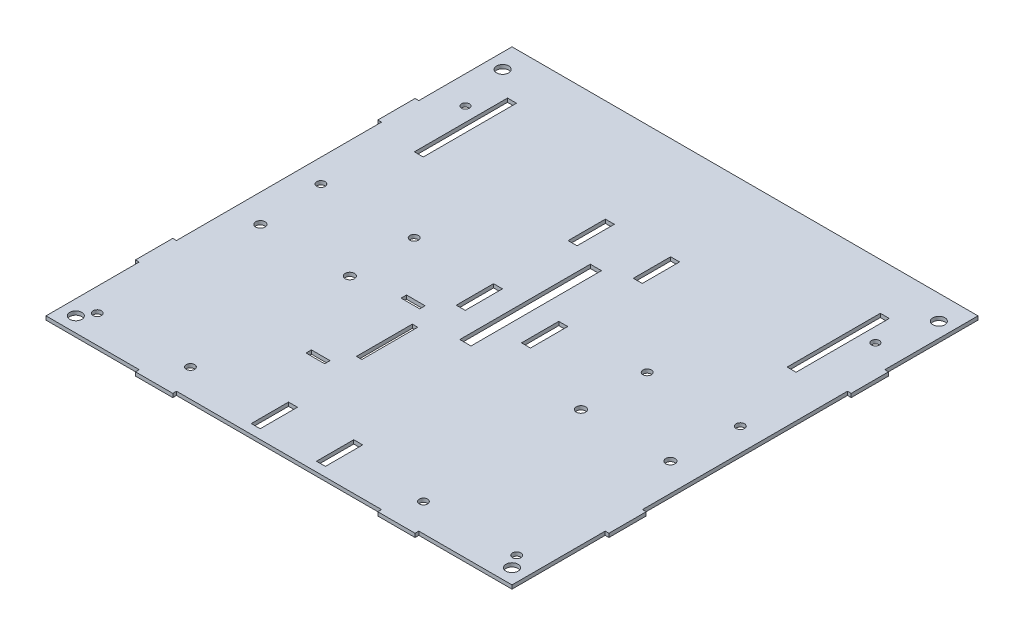
SolidWorks part; units mm, degrees
ref_plane "Front Plane" through (0, 0, 0) normal (0, 0, 1) x (1, 0, 0)
ref_plane "Top Plane" through (0, 0, 0) normal (0, 1, 0) x (1, 0, 0)
ref_plane "Right Plane" through (0, 0, 0) normal (1, 0, 0) x (0, 0, -1)
sketch "Sketch1" plane through (0, 0, 0) normal (0, 1, 0) x (1, 0, 0)
  line L0 (144.9, 25) -> (144.9, 5)
  line L1 (144.9, 5) -> (140.1, 5)
  line L2 (140.1, 25) -> (144.9, 25)
  line L3 (140.1, 5) -> (140.1, 25)
  line L4 (109.9, 5) -> (109.9, 25)
  line L5 (109.9, 25) -> (105.1, 25)
  line L6 (105.1, 25) -> (105.1, 5)
  line L7 (105.1, 5) -> (109.9, 5)
  line L8 (87, 52.4842) -> (97, 52.4842)
  line L9 (97, 55.3842) -> (97, 52.4842)
  line L10 (87, 55.3842) -> (97, 55.3842)
  line L11 (87, 52.4842) -> (87, 55.3842)
  line L12 (105, 64.4342) -> (102.1, 64.4342)
  line L13 (105, 64.4342) -> (105, 94.4342)
  line L14 (102.1, 94.4342) -> (102.1, 64.4342)
  line L15 (102.1, 94.4342) -> (105, 94.4342)
  line L16 (97, 106.3842) -> (97, 103.4842)
  line L17 (97, 106.3842) -> (87, 106.3842)
  line L18 (87, 103.4842) -> (97, 103.4842)
  line L19 (87, 103.4842) -> (87, 106.3842)
  line L20 (109.9, 135) -> (105.1, 135)
  line L21 (109.9, 115) -> (109.9, 135)
  line L22 (105.1, 135) -> (105.1, 115)
  line L23 (105.1, 115) -> (109.9, 115)
  line L24 (144.9, 115) -> (140.1, 115)
  line L25 (140.1, 115) -> (140.1, 135)
  line L26 (144.9, 135) -> (144.9, 115)
  line L27 (140.1, 135) -> (144.9, 135)
  line L28 (227.4, 175) -> (227.4, 225)
  line L29 (222.6, 175) -> (222.6, 225)
  line L30 (227.4, 225) -> (222.6, 225)
  line L31 (222.6, 175) -> (227.4, 175)
  line L32 (125, 100) -> (125, 170) construction
  line L33 (122, 170) -> (128, 170)
  line L34 (122, 170) -> (122, 100)
  line L35 (122, 100) -> (128, 100)
  line L36 (22.6, 225) -> (27.4, 225)
  line L37 (27.4, 225) -> (27.4, 175)
  line L38 (22.6, 175) -> (22.6, 225)
  line L39 (27.4, 175) -> (22.6, 175)
  line L40 (250, 250) -> (0, 250)
  line L41 (0, 250) -> (0, 0)
  line L42 (0, 0) -> (250, 0)
  line L43 (250, 0) -> (250, 250)
  line L44 (128, 170) -> (128, 100)
  dimension "D2" = 22.6
  dimension "D3" = 5.1
  dimension "D4" = 10
  dimension "D5" = 102.1
  dimension "D6" = 2.9
  dimension "D7" = 27.4
  dimension "D8" = 105.1
  dimension "D9" = 4.8
  dimension "D10" = 140.1
  dimension "D11" = 222.6
  dimension "D12" = 5
  dimension "D13" = 25
  dimension "D14" = 52.4842
  dimension "D15" = 250
  dimension "D16" = 64.4342
  dimension "D17" = 103.4842
  dimension "D18" = 94.4342
  dimension "D19" = 115
  dimension "D20" = 50
  dimension "D21" = 6
  dimension "D22" = 70
  dimension "D23" = 175
  dimension "D24" = 125
  dimension "D25" = 250
  dimension "D26" = 80
extrude "Boss-Extrude1" add sketch "Sketch1" along normal blind 2
sketch "Sketch2" plane through (0, 2, 0) normal (0, 1, 0) x (1, 0, 0)
  line L0 (0, 250) -> (0, 0) construction
  line L1 (0, 0) -> (250, 0) construction
  circle A0 centre (15, 100) radius 2.5
  circle A1 centre (63, 100) radius 2.5
  dimension "D1" = 5
  dimension "D2" = 5
  dimension "D3" = 48
  dimension "D4" = 15
  dimension "D5" = 100
extrude "Cut-Extrude1" cut sketch "Sketch2" against normal through all
sketch "Sketch3" plane through (0, 2, 0) normal (0, 1, 0) x (1, 0, 0)
  line L3 (250, 0) -> (250, 250) construction
  circle A0 centre (8, 8) radius 3.25
  circle A1 centre (8, 237) radius 3.25
  dimension "D1" = 6.5
  dimension "D2" = 242
  dimension "D3" = 212
  dimension "D4" = 17
extrude "Cut-Extrude2" cut sketch "Sketch3" against normal through all
ref_plane "Plane1" through (125, 0, 0) normal (-1, 0, 0) x (0, 0, 1)
mirror "Mirror1" about plane through (125, 0, 0) normal (-1, 0, 0) of "Cut-Extrude2"
sketch "Sketch4" plane through (0, 2, 0) normal (0, 1, 0) x (1, 0, 0)
  line L1 (0, 200) -> (-2, 200)
  line L2 (0, 200) -> (0, 180)
  line L3 (0, 180) -> (-2, 180)
  line L4 (-2, 200) -> (-2, 180)
  line L7 (0, 70) -> (-2, 70)
  line L8 (0, 70) -> (0, 50)
  line L9 (0, 50) -> (-2, 50)
  line L10 (-2, 70) -> (-2, 50)
  line L11 (144.9, 5) -> (144.9, 25) construction
  line L12 (50, 0) -> (70, 0)
  line L13 (50, 0) -> (50, -2)
  line L14 (50, -2) -> (70, -2)
  line L15 (70, 0) -> (70, -2)
  line L16 (144.9, 25) -> (140.1, 25) construction
  dimension "D1" = 74.9
  dimension "D2" = 94.9
  dimension "D3" = 144.9
  dimension "D4" = 146.9
  dimension "D5" = 25
  dimension "D6" = 155
  dimension "D7" = 25
extrude "Boss-Extrude2" add sketch "Sketch4" against normal up to vertex (2 mm away) up to point (0, 0, 0)
mirror "Mirror2" about plane through (125, 0, 0) normal (-1, 0, 0) of "Boss-Extrude2"
mirror "Mirror3" about plane through (125, 0, 0) normal (-1, 0, 0) of "Cut-Extrude1"
hole_wizard "Ø4.5 (4.5) Diameter Hole1" positions "Sketch7" profile "Sketch6" hole size "Ø4.5" standard "ISO"
sketch "Sketch7" plane through (0, 2, 0) normal (0, 1, 0) x (1, 0, 0)
  line L0 (252, 200) -> (252, 180) construction
  line L1 (250, 200) -> (252, 200) construction
  point P0 (12.5, 135)
  point P3 (62.5, 135)
  point P6 (62.5, 15)
  point P9 (12.5, 15)
  dimension "D1" = 189.5
  dimension "D2" = 239.5
  dimension "D3" = 65
  dimension "D4" = 185
sketch "Sketch6" plane through (12.5, 2, -135) normal (1, 0, 0) x (0, 0, 1)
  line L0 (0, 0) -> (0, 11.3519)
  line L1 (0, 11.3519) -> (2.25, 10)
  line L2 (2.25, 10) -> (2.25, 0)
  line L5 (2.25, 0) -> (0, 0)
  line L10 (0, 11.3519) -> (-2.25, 10) construction
  line L11 (0, -6.35) -> (0, 107.95) construction
  dimension "Hole Dia." = 4.5
  dimension "Hole Depth" = 10
  dimension "Drill Angle" = 118
mirror "Mirror4" about plane through (125, 0, 0) normal (-1, 0, 0) of "Ø4.5 (4.5) Diameter Hole1"
sketch "Sketch9" plane through (0, 0, 0) normal (0, -1, 0) x (1, 0, 0)
  line L0 (105, -175) -> (110, -175) construction
  line L1 (105.1, -175) -> (109.9, -175)
  line L2 (105.1, -175) -> (105.1, -195)
  line L3 (105.1, -195) -> (109.9, -195)
  line L4 (109.9, -175) -> (109.9, -195)
  line L5 (105, -195) -> (110, -195) construction
  line L6 (105, -175) -> (105, -195) construction
  dimension "D1" = 4.8
  dimension "D2" = 0.1
extrude "Cut-Extrude3" cut sketch "Sketch9" against normal through all
mirror "Mirror5" about plane through (125, 0, 0) normal (-1, 0, 0) of "Cut-Extrude3"
sketch "Sketch10" plane through (0, 0, 0) normal (0, -1, 0) x (1, 0, 0)
  line L0 (0, -250) -> (0, 4.2) construction
  line L1 (250, -250) -> (0, -250) construction
  line L2 (250, -250) -> (250, 4.2) construction
  circle A0 centre (15, -210) radius 2.1
  circle A1 centre (235, -210) radius 2.1
  dimension "D1" = 4.2
  dimension "D2" = 15
  dimension "D3" = 40
  dimension "D4" = 15
extrude "Cut-Extrude4" cut sketch "Sketch10" against normal blind 5
